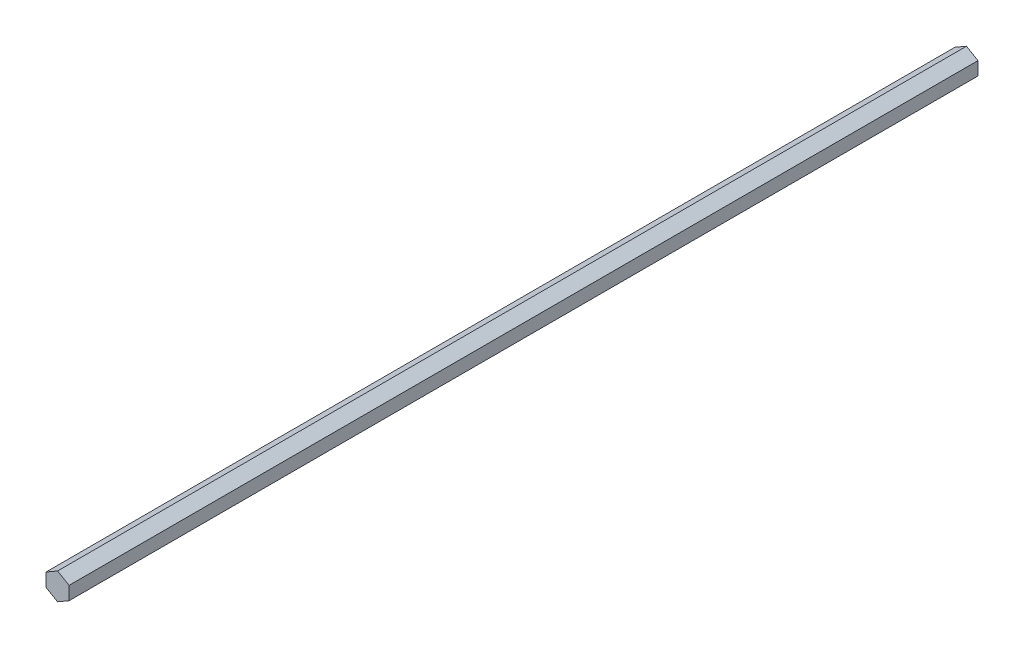
SolidWorks part; units mm, degrees
ref_plane "Front Plane" through (0, 0, 0) normal (0, 0, 1) x (1, 0, 0)
ref_plane "Top Plane" through (0, 0, 0) normal (0, 1, 0) x (1, 0, 0)
ref_plane "Right Plane" through (0, 0, 0) normal (1, 0, 0) x (0, 0, -1)
sketch "Sketch1" plane through (0, 0, 0) normal (0, 0, 1) x (1, 0, 0)
  line L1 (0, 7.3323) -> (-6.35, 3.6662)
  line L2 (-6.35, 3.6662) -> (-6.35, -3.6662)
  line L3 (-6.35, -3.6662) -> (0, -7.3323)
  line L4 (0, -7.3323) -> (6.35, -3.6662)
  line L5 (6.35, -3.6662) -> (6.35, 3.6662)
  line L6 (6.35, 3.6662) -> (0, 7.3323)
  circle A0 centre (0, 0) radius 6.35 construction
  point P1 (0, 0)
  dimension "D1" = 12.7
extrude "Boss-Extrude1" add sketch "Sketch1" along normal blind 500
ref_axis "Axis1" through (0, 0, 0) along (0, 0, 1)
